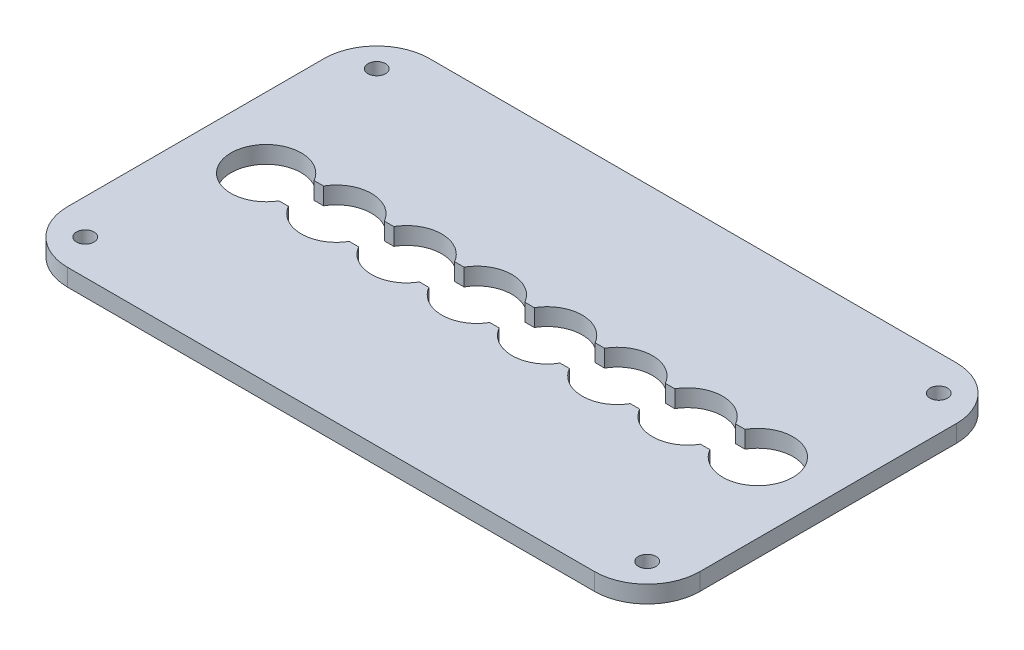
SolidWorks part; units mm, degrees
ref_plane "Alzado" through (0, 0, 0) normal (0, 0, 1) x (1, 0, 0)
ref_plane "Planta" through (0, 0, 0) normal (0, 1, 0) x (1, 0, 0)
ref_plane "Vista lateral" through (0, 0, 0) normal (1, 0, 0) x (0, 0, -1)
sketch "Croquis1" plane through (0, 0, 0) normal (0, 0, 1) x (1, 0, 0)
  line L0 (0, 0) -> (0, -5)
  line L1 (15, -20) -> (337, -20)
  line L2 (352, -5) -> (352, 0)
  line L3 (-15, 0) -> (-15, -5)
  line L4 (15, -35) -> (337, -35)
  line L5 (367, -5) -> (367, 0)
  line L6 (-15, 0) -> (0, 0)
  line L7 (352, 0) -> (367, 0)
  arc A0 (352, -5) -> (337, -20) centre (337, -5) cw
  arc A1 (0, -5) -> (15, -20) centre (15, -5) ccw
  arc A2 (-15, -5) -> (15, -35) centre (15, -5) ccw
  arc A3 (367, -5) -> (337, -35) centre (337, -5) cw
  dimension "D1" = 15
  dimension "D2" = 5
  dimension "D4" = 352
  dimension "D3" = 15
extrude "Saliente-Extruir1" add sketch "Croquis1" along normal blind 103
sketch "Croquis2" plane through (0, 0, 0) normal (0, 1, 0) x (1, 0, 0)
  line L0 (0, -103) -> (0, 0) construction
  line L1 (-10, -25.1459) -> (-5, -25.1459)
  line L2 (-10, -25.1459) -> (-10, -75.1459)
  line L3 (-10, -75.1459) -> (-5, -75.1459)
  line L4 (-5, -25.1459) -> (-5, -75.1459)
  line L5 (357, -11.5) -> (362, -11.5)
  line L6 (357, -11.5) -> (357, -91.5)
  line L7 (357, -91.5) -> (362, -91.5)
  line L8 (362, -11.5) -> (362, -91.5)
  line L9 (352, -103) -> (352, 0) construction
  line L10 (352, 0) -> (352, -103) construction
  point P12 (362, -51.5)
  point P17 (352, -51.5)
  dimension "D1" = 5
  dimension "D2" = 50
  dimension "D3" = 5
  dimension "D4" = 80
  dimension "D5" = 5
  dimension "D6" = 5
extrude "Saliente-Extruir2" add sketch "Croquis2" along normal blind 35
fillet "Redondeo1" radius 5 8 edges at (362, 0, 51.5) (359.5, 0, 91.5) (357, 0, 51.5) (359.5, 0, 11.5) (-7.5, 0, 25.1459) (-10, 0, 50.1459) (-7.5, 0, 75.1459) (-5, 0, 50.1459)
fillet "Redondeo2" radius 5 4 edges at (-7.5, 35, 25.1459) (-7.5, 35, 75.1459) (359.5, 35, 11.5) (359.5, 35, 91.5)
ref_plane "Plano1" through (15, 0, 0) normal (1, 0, 0) x (0, 0, -1)
sketch "Croquis3" plane through (15, 0, 0) normal (1, 0, 0) x (0, 0, -1)
  line L0 (-103, -35) -> (0, -35) construction
  line L1 (-76.5, -35) -> (-70.5, -35)
  line L2 (-76.5, -35) -> (-76.5, -43)
  line L3 (-76.5, -43) -> (-26.5, -43)
  line L4 (-26.5, -35) -> (-26.5, -43)
  line L5 (-103, -35) -> (-70.5, -35) construction
  line L6 (-51.5, -33) -> (-51.5, -5) construction
  line L7 (-103, -5) -> (0, -5) construction
  line L8 (-32.5, -35) -> (-26.5, -35)
  line L10 (-70.5, -35) -> (-70.5, -37)
  line L11 (-70.5, -37) -> (-32.5, -37)
  line L12 (-32.5, -35) -> (-32.5, -37)
  line L13 (-51.5, -35) -> (-32.5, -37) construction
  line L14 (-70.5, -37) -> (-51.5, -35) construction
  line L15 (-32.5, -35) -> (0, -35) construction
  dimension "D1" = 50
  dimension "D2" = 8
  dimension "D3" = 38
extrude "Saliente-Extruir3" add sketch "Croquis3" along normal up to vertex (322 mm away) up to point (337, -35, 103)
fillet "Redondeo4" radius 10 2 edges at (176, -35, 76.5) (176, -35, 26.5)
fillet "Redondeo5" radius 10 2 edges at (176, -43, 26.5) (176, -43, 76.5)
sketch "Croquis4" plane through (0, 0, 103) normal (0, 0, 1) x (1, 0, 0)
  line L0 (176, -43) -> (176, 89.8456) construction
  line L1 (337, -43) -> (15, -43) construction
  line L3 (176, 89.8456) -> (296, 89.8456)
  line L4 (176, 89.8456) -> (176, -75.5918)
  line L5 (176, -75.5918) -> (296, -75.5918)
  line L6 (296, 89.8456) -> (296, -75.5918)
  dimension "D1" = 120
extrude "Cortar-Extruir1" cut sketch "Croquis4" against normal through all both and the other way through all
sketch "Croquis8" plane through (296, 0, 0) normal (-1, 0, 0) x (0, 0, 1)
  line L1 (103, -20) -> (0, -20)
  line L2 (103, -20) -> (103, -27)
  line L3 (103, -27) -> (0, -27)
  line L4 (0, -20) -> (0, -27)
  dimension "D1" = 7
extrude "Saliente-Extruir5" add sketch "Croquis8" along normal blind 200
fillet "Redondeo6" radius 15 2 edges at (96, -23.5, 0) (96, -23.5, 103)
sketch "Croquis9" plane through (0, -27, 0) normal (0, -1, 0) x (1, 0, 0)
  line L2 (96, 51.5) -> (106, 51.5) construction
  line L19 (96, 15) -> (96, 88) construction
  line L26 (144.6603, 56.5) -> (147.3397, 56.5)
  line L27 (124.6603, 46.5) -> (127.3397, 46.5)
  line L37 (124.6603, 56.5) -> (127.3397, 56.5)
  line L45 (144.6603, 46.5) -> (147.3397, 46.5)
  line L46 (204.6603, 56.5) -> (207.3397, 56.5)
  line L47 (164.6603, 56.5) -> (167.3397, 56.5)
  line L48 (164.6603, 46.5) -> (167.3397, 46.5)
  line L50 (184.6603, 56.5) -> (187.3397, 56.5)
  line L51 (184.6603, 46.5) -> (187.3397, 46.5)
  line L53 (204.6603, 46.5) -> (207.3397, 46.5)
  line L54 (224.6603, 46.5) -> (227.3397, 46.5)
  line L55 (224.6603, 56.5) -> (227.3397, 56.5)
  line L56 (244.6603, 46.5) -> (247.3397, 46.5)
  line L57 (244.6603, 56.5) -> (247.3397, 56.5)
  arc A33 (127.3397, 46.5) -> (144.6603, 46.5) centre (136, 51.5) ccw
  arc A34 (147.3397, 46.5) -> (164.6603, 46.5) centre (156, 51.5) ccw
  arc A35 (167.3397, 46.5) -> (184.6603, 46.5) centre (176, 51.5) ccw
  arc A36 (187.3397, 46.5) -> (204.6603, 46.5) centre (196, 51.5) ccw
  arc A38 (244.6603, 56.5) -> (227.3397, 56.5) centre (236, 51.5) ccw
  arc A39 (247.3397, 46.5) -> (247.3397, 56.5) centre (256, 51.5) ccw
  arc A41 (124.6603, 56.5) -> (124.6603, 46.5) centre (116, 51.5) ccw
  arc A42 (144.6603, 56.5) -> (127.3397, 56.5) centre (136, 51.5) ccw
  arc A43 (204.6603, 56.5) -> (187.3397, 56.5) centre (196, 51.5) ccw
  arc A44 (207.3397, 46.5) -> (224.6603, 46.5) centre (216, 51.5) ccw
  arc A45 (164.6603, 56.5) -> (147.3397, 56.5) centre (156, 51.5) ccw
  arc A46 (227.3397, 46.5) -> (244.6603, 46.5) centre (236, 51.5) ccw
  arc A47 (184.6603, 56.5) -> (167.3397, 56.5) centre (176, 51.5) ccw
  arc A49 (224.6603, 56.5) -> (207.3397, 56.5) centre (216, 51.5) ccw
  point P8 (186, 51.5)
  dimension "D2" = 20
sketch "Croquis10" plane through (362, 0, 0) normal (1, 0, 0) x (0, 0, -1)
  line L0 (-51.5, 35) -> (-51.5, 2.6584) construction
  line L1 (-86.5, 35) -> (-16.5, 35) construction
  line L2 (-80.5, 20) -> (-22.5, 20) construction
  circle A0 centre (-80.5, 20) radius 2.5
  circle A1 centre (-22.5, 20) radius 2.5
  point P4 (-51.5, 20)
  dimension "D1" = 58
  dimension "D3" = 5
  dimension "D4" = 5
  dimension "D2" = 15
extrude "Cortar-Extruir5" cut sketch "Croquis10" against normal through all
extrude "Cortar-Extruir6" cut sketch "Croquis9" against normal blind 10
sketch "Croquis11" plane through (0, -27, 0) normal (0, -1, 0) x (1, 0, 0)
  line L0 (247.3397, 56.5) -> (244.6603, 56.5) construction
  line L1 (244.6603, 46.5) -> (247.3397, 46.5) construction
  line L2 (227.3397, 56.5) -> (224.6603, 56.5) construction
  line L3 (224.6603, 46.5) -> (227.3397, 46.5) construction
  line L8 (96, 88) -> (96, 15)
  line L9 (111, 0) -> (296, 0)
  line L10 (296, 0) -> (296, 103)
  line L11 (296, 103) -> (111, 103)
  line L12 (96, 88) -> (96, 15)
  line L13 (111, 0) -> (296, 0)
  line L14 (296, 0) -> (296, 103)
  line L15 (296, 103) -> (111, 103)
  line L28 (207.3397, 56.5) -> (204.6603, 56.5) construction
  line L29 (204.6603, 46.5) -> (207.3397, 46.5) construction
  line L30 (184.6603, 46.5) -> (187.3397, 46.5) construction
  line L31 (187.3397, 56.5) -> (184.6603, 56.5) construction
  line L32 (164.6603, 46.5) -> (167.3397, 46.5) construction
  line L33 (167.3397, 56.5) -> (164.6603, 56.5) construction
  line L34 (147.3397, 56.5) -> (144.6603, 56.5) construction
  line L35 (144.6603, 46.5) -> (147.3397, 46.5) construction
  line L36 (124.6603, 46.5) -> (127.3397, 46.5) construction
  line L37 (127.3397, 56.5) -> (124.6603, 56.5) construction
  line L38 (247.3397, 56.5) -> (244.6603, 56.5)
  line L39 (244.6603, 46.5) -> (247.3397, 46.5)
  line L40 (227.3397, 56.5) -> (224.6603, 56.5)
  line L41 (224.6603, 46.5) -> (227.3397, 46.5)
  line L42 (207.3397, 56.5) -> (204.6603, 56.5)
  line L43 (204.6603, 46.5) -> (207.3397, 46.5)
  line L44 (184.6603, 46.5) -> (187.3397, 46.5)
  line L45 (187.3397, 56.5) -> (184.6603, 56.5)
  line L46 (164.6603, 46.5) -> (167.3397, 46.5)
  line L47 (167.3397, 56.5) -> (164.6603, 56.5)
  line L48 (147.3397, 56.5) -> (144.6603, 56.5)
  line L49 (144.6603, 46.5) -> (147.3397, 46.5)
  line L50 (124.6603, 46.5) -> (127.3397, 46.5)
  line L51 (127.3397, 56.5) -> (124.6603, 56.5)
  arc A0 (247.3397, 46.5) -> (247.3397, 56.5) centre (256, 51.5) ccw construction
  arc A1 (227.3397, 46.5) -> (244.6603, 46.5) centre (236, 51.5) ccw construction
  arc A4 (96, 15) -> (111, 0) centre (111, 15) ccw
  arc A5 (111, 103) -> (96, 88) centre (111, 88) ccw
  arc A6 (96, 15) -> (111, 0) centre (111, 15) ccw
  arc A7 (111, 103) -> (96, 88) centre (111, 88) ccw
  arc A22 (244.6603, 56.5) -> (227.3397, 56.5) centre (236, 51.5) ccw construction
  arc A23 (207.3397, 46.5) -> (224.6603, 46.5) centre (216, 51.5) ccw construction
  arc A24 (204.6603, 56.5) -> (187.3397, 56.5) centre (196, 51.5) ccw construction
  arc A25 (224.6603, 56.5) -> (207.3397, 56.5) centre (216, 51.5) ccw construction
  arc A26 (187.3397, 46.5) -> (204.6603, 46.5) centre (196, 51.5) ccw construction
  arc A27 (184.6603, 56.5) -> (167.3397, 56.5) centre (176, 51.5) ccw construction
  arc A28 (167.3397, 46.5) -> (184.6603, 46.5) centre (176, 51.5) ccw construction
  arc A29 (147.3397, 46.5) -> (164.6603, 46.5) centre (156, 51.5) ccw construction
  arc A30 (164.6603, 56.5) -> (147.3397, 56.5) centre (156, 51.5) ccw construction
  arc A31 (127.3397, 46.5) -> (144.6603, 46.5) centre (136, 51.5) ccw construction
  arc A32 (144.6603, 56.5) -> (127.3397, 56.5) centre (136, 51.5) ccw construction
  arc A33 (124.6603, 56.5) -> (124.6603, 46.5) centre (116, 51.5) ccw construction
  arc A34 (247.3397, 46.5) -> (247.3397, 56.5) centre (256, 51.5) ccw
  arc A35 (227.3397, 46.5) -> (244.6603, 46.5) centre (236, 51.5) ccw
  arc A36 (244.6603, 56.5) -> (227.3397, 56.5) centre (236, 51.5) ccw
  arc A37 (207.3397, 46.5) -> (224.6603, 46.5) centre (216, 51.5) ccw
  arc A38 (204.6603, 56.5) -> (187.3397, 56.5) centre (196, 51.5) ccw
  arc A39 (224.6603, 56.5) -> (207.3397, 56.5) centre (216, 51.5) ccw
  arc A40 (187.3397, 46.5) -> (204.6603, 46.5) centre (196, 51.5) ccw
  arc A41 (184.6603, 56.5) -> (167.3397, 56.5) centre (176, 51.5) ccw
  arc A42 (167.3397, 46.5) -> (184.6603, 46.5) centre (176, 51.5) ccw
  arc A43 (147.3397, 46.5) -> (164.6603, 46.5) centre (156, 51.5) ccw
  arc A44 (164.6603, 56.5) -> (147.3397, 56.5) centre (156, 51.5) ccw
  arc A45 (127.3397, 46.5) -> (144.6603, 46.5) centre (136, 51.5) ccw
  arc A46 (144.6603, 56.5) -> (127.3397, 56.5) centre (136, 51.5) ccw
  arc A47 (124.6603, 56.5) -> (124.6603, 46.5) centre (116, 51.5) ccw
  dimension "D1" = 0
extrude "Saliente-Extruir6" add sketch "Croquis11" against normal blind 12
sketch "Croquis12" plane through (296, 0, 0) normal (1, 0, 0) x (0, 0, -1)
  line L4 (-103, -20) -> (0, -20)
  line L5 (0, -20) -> (0, -15)
  line L6 (0, -15) -> (-103, -15)
  line L7 (-103, -15) -> (-103, -20)
  line L8 (-103, -20) -> (0, -20)
  line L9 (0, -20) -> (0, -15)
  line L10 (0, -15) -> (-103, -15)
  line L11 (-103, -15) -> (-103, -20)
  dimension "D1" = 0
extrude "Saliente-Extruir7" add sketch "Croquis12" along normal up to vertex (41 mm away) up to point (337, -20, 103)
fillet "Redondeo7" radius 10 1 edges at (337, -15, 51.5)
sketch "Croquis13" plane through (0, 0, 103) normal (0, 0, 1) x (1, 0, 0)
  line L1 (296, -27) -> (84.0172, -27)
  line L2 (296, -27) -> (296, -20)
  line L3 (296, -20) -> (84.0172, -20)
  line L4 (84.0172, -27) -> (84.0172, -20)
  dimension "D1" = 7
extrude "Cortar-Extruir7" cut sketch "Croquis13" against normal through all both and the other way through all
fillet "Redondeo8" radius 5 1 edges at (296, -20, 51.5)
sketch "Croquis14" plane through (0, -20, 0) normal (0, -1, 0) x (1, 0, 0)
  line L0 (291, 0) -> (111, 0) construction
  line L1 (291, 103) -> (266, 103) construction
  line L2 (291, 103) -> (291, 0) construction
  line L3 (291, 0) -> (266, 0) construction
  line L4 (266, 103) -> (266, 0) construction
  line L5 (276, 103) -> (276, 0) construction
  line L6 (96, 15) -> (96, 88) construction
  line L7 (276, 103) -> (378.6728, 103)
  line L8 (276, 103) -> (276, -9.095)
  line L9 (276, -9.095) -> (378.6728, -9.095)
  line L10 (378.6728, 103) -> (378.6728, -9.095)
  arc A0 (247.3397, 46.5) -> (247.3397, 56.5) centre (256, 51.5) ccw construction
  dimension "D1" = 180
extrude "Cortar-Extruir9" cut sketch "Croquis14" against normal through all both and the other way through all
fillet "Redondeo9" radius 15 2 edges at (276, -17.5, 0) (276, -17.5, 103)
sketch "Croquis15" plane through (0, -20, 0) normal (0, -1, 0) x (1, 0, 0)
  line L0 (186, 103) -> (186, 0) construction
  line L1 (261, 103) -> (111, 103) construction
  line L2 (261, 0) -> (111, 0) construction
  line L3 (96, 15) -> (96, 88) construction
  line L4 (186, 51.5) -> (96, 51.5) construction
  line L5 (106, 93) -> (106, 10) construction
  line L6 (266, 93) -> (266, 10) construction
  circle A0 centre (106, 93) radius 2.5
  circle A1 centre (106, 10) radius 2.5
  circle A2 centre (266, 10) radius 2.5
  circle A3 centre (266, 93) radius 2.5
  point P15 (106, 51.5)
  dimension "D1" = 5
  dimension "D2" = 5
  dimension "D3" = 10
  dimension "D4" = 10
  dimension "D5" = 83
extrude "Cortar-Extruir10" cut sketch "Croquis15" against normal through all both and the other way through all
sketch "Croquis16" plane through (0, -20, 0) normal (0, -1, 0) x (1, 0, 0)
  line L4 (111, 0) -> (261, 0)
  line L5 (276, 15) -> (276, 88)
  line L6 (261, 103) -> (111, 103)
  line L7 (96, 88) -> (96, 15)
  line L8 (111, 0) -> (261, 0)
  line L9 (276, 15) -> (276, 88)
  line L10 (261, 103) -> (111, 103)
  line L11 (96, 88) -> (96, 15)
  arc A4 (261, 0) -> (276, 15) centre (261, 15) ccw
  arc A5 (276, 88) -> (261, 103) centre (261, 88) ccw
  arc A6 (111, 103) -> (96, 88) centre (111, 88) ccw
  arc A7 (96, 15) -> (111, 0) centre (111, 15) ccw
  arc A8 (261, 0) -> (276, 15) centre (261, 15) ccw
  arc A9 (276, 88) -> (261, 103) centre (261, 88) ccw
  arc A10 (111, 103) -> (96, 88) centre (111, 88) ccw
  arc A11 (96, 15) -> (111, 0) centre (111, 15) ccw
  dimension "D1" = 0
extrude "Cortar-Extruir11" cut sketch "Croquis16" against normal blind 0.1
